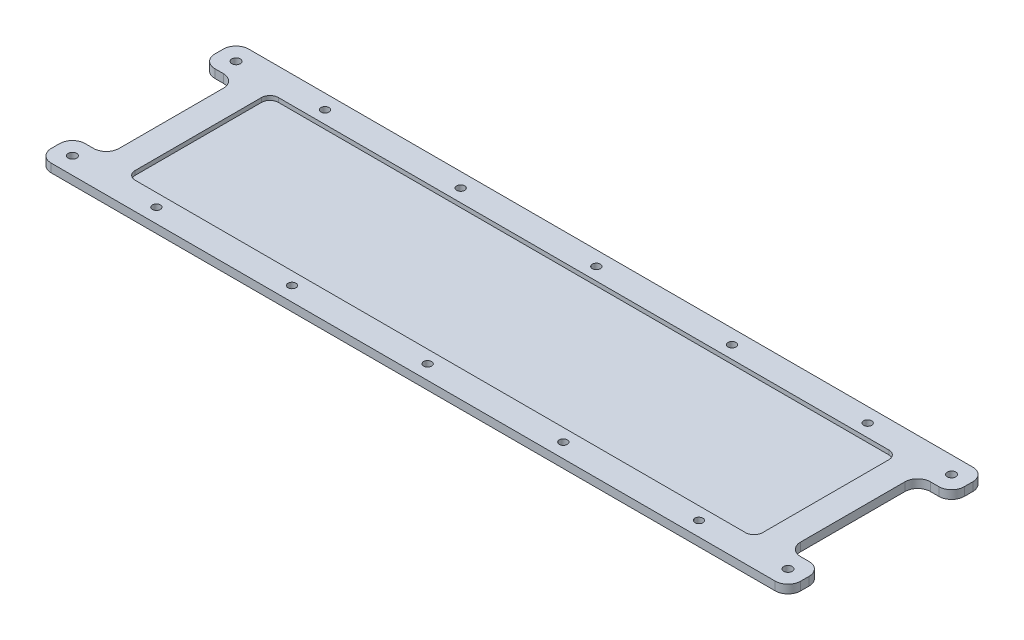
SolidWorks part; units mm, degrees
ref_plane "Front Plane" through (0, 0, 0) normal (0, 0, 1) x (1, 0, 0)
ref_plane "Top Plane" through (0, 0, 0) normal (0, 1, 0) x (1, 0, 0)
ref_plane "Right Plane" through (0, 0, 0) normal (1, 0, 0) x (0, 0, -1)
sketch "Sketch1" plane through (0, 0, 0) normal (0, 1, 0) x (1, 0, 0)
  line L0 (3.81, 3.81) -> (3.81, 70.1599) construction
  line L1 (0, 0) -> (255.27, 0)
  line L2 (0, 0) -> (0, 73.9699)
  line L3 (0, 73.9699) -> (255.27, 73.9699)
  line L4 (255.27, 0) -> (255.27, 73.9699)
  line L5 (6.985, 66.9849) -> (195.485, 66.9849) construction
  line L6 (6.985, 66.9849) -> (6.985, 6.985) construction
  line L7 (6.985, 6.985) -> (195.485, 6.985) construction
  line L8 (195.485, 66.9849) -> (195.485, 6.985) construction
  line L9 (3.81, 70.1599) -> (251.46, 70.1599) construction
  line L10 (251.46, 3.81) -> (251.46, 70.1599) construction
  line L11 (3.81, 3.81) -> (251.46, 3.81) construction
  line L12 (565.2908, 402.2635) -> (1930.6241, 402.2635) construction
  line L28 (127.635, 73.9699) -> (127.635, 0) construction
  line L29 (127.635, 70.1599) -> (127.635, 66.9849) construction
  line L30 (0, 36.9849) -> (255.27, 36.9849) construction
  circle A0 centre (178.435, 68.5724) radius 1.5
  circle A1 centre (178.435, 5.3975) radius 1.5
  circle A2 centre (229.235, 68.5724) radius 1.5
  circle A3 centre (229.235, 5.3975) radius 1.5
  circle A4 centre (214.6468, 59.9999) radius 3.81 construction
  circle A15 centre (127.635, 68.5724) radius 1.5
  circle A20 centre (127.635, 5.3975) radius 1.5
  circle A21 centre (26.035, 5.3975) radius 1.5
  circle A22 centre (76.835, 5.3975) radius 1.5
  circle A23 centre (26.035, 68.5724) radius 1.5
  circle A24 centre (76.835, 68.5724) radius 1.5
  point P48 (127.635, 68.5724)
  dimension "D6" = 3.175
  dimension "D11" = 7.62
  dimension "D13" = 188.5
  dimension "D15" = 3
  dimension "D1" = 59.9999
  dimension "D2" = 3.175
  dimension "D3" = 3.175
  dimension "D4" = 3.81
  dimension "D5" = 3.81
  dimension "D7" = 3.81
  dimension "D8" = 3.81
  dimension "D9" = 19.1618
  dimension "D10" = 10.16
  dimension "D12" = 73.9699
  dimension "D14" = 55.975
  dimension "D16" = 3
  dimension "D17" = 50.8
extrude "Boss-Extrude1" add sketch "Sketch1" along normal blind 1.5875 and the other way blind 1.5875 contours L4 | L2 | L1 L4 L3 L2 A23 A22 A21 A3 A2 A0 A1 A15 A20 A24 region at (127.635, 0, -36.9849)
extrude "Boss-Extrude2" add sketch "Sketch1<4>" along normal blind 1.5875 and the other way blind 1.5875 contours L1 L4 L3 L2
sketch "Sketch1<4>" plane through (0, 0, 0) normal (0, 1, 0) x (1, 0, 0) same geometry as "Sketch1"
sketch "Sketch2" plane through (0, 1.5875, 0) normal (0, 1, 0) x (1, 0, 0)
  line L0 (6.985, 66.9849) -> (195.485, 66.9849) construction
  line L1 (13.335, 63.8099) -> (241.935, 63.8099)
  line L2 (10.16, 60.6349) -> (10.16, 13.335)
  line L3 (13.335, 10.16) -> (241.935, 10.16)
  line L4 (245.11, 60.6349) -> (245.11, 13.335)
  line L5 (6.985, 6.985) -> (195.485, 6.985) construction
  line L6 (6.985, 66.9849) -> (6.985, 6.985) construction
  line L7 (251.46, 3.81) -> (251.46, 70.1599) construction
  line L8 (0, 73.9699) -> (255.27, 73.9699) construction
  arc A0 (241.935, 63.8099) -> (245.11, 60.6349) centre (241.935, 60.6349) cw
  arc A1 (245.11, 13.335) -> (241.935, 10.16) centre (241.935, 13.335) cw
  arc A2 (13.335, 10.16) -> (10.16, 13.335) centre (13.335, 13.335) cw
  arc A3 (13.335, 63.8099) -> (10.16, 60.6349) centre (13.335, 60.6349) ccw
  dimension "D6" = 3.175
  dimension "D1" = 3.175
  dimension "D2" = 3.175
  dimension "D3" = 3.175
  dimension "D4" = 6.35
  dimension "D5" = 10.16
extrude "Cut-Extrude1" cut sketch "Sketch2" against normal blind 1.5875
extrude "Cut-Extrude2" cut sketch "Sketch1<6>" against normal blind 3.175 and the other way blind 3.175 contours A2 | A3 | A1 | A0 | A15 | A24 | A22 | A20 | A21 | A23
sketch "Sketch1<6>" plane through (0, 0, 0) normal (0, 1, 0) x (1, 0, 0) same geometry as "Sketch1"
sketch "Sketch3" plane through (0, -1.5875, 0) normal (0, -1, 0) x (1, 0, 0)
  line L0 (127.635, -36.9849) -> (127.635, 0) construction
  line L5 (0, 0) -> (0, -73.9699) construction
  line L6 (0, -17.4625) -> (0, 0)
  line L8 (0, 0) -> (-7.9375, 0)
  line L9 (0, -36.9849) -> (255.27, -36.9849) construction
  line L10 (255.27, 0) -> (255.27, -73.9699) construction
  line L11 (0, 0) -> (255.27, 0) construction
  line L12 (-12.7, -4.7625) -> (-12.7, -7.9375)
  line L13 (-7.9375, -12.7) -> (-4.7625, -12.7)
  line L14 (-12.7, -6.35) -> (0, -6.35) construction
  line L15 (-12.7, -67.6199) -> (0, -67.6199) construction
  line L16 (-7.9375, -61.2699) -> (-4.7625, -61.2699)
  line L17 (-12.7, -69.2074) -> (-12.7, -66.0324)
  line L18 (0, -73.9699) -> (-7.9375, -73.9699)
  line L19 (0, -56.5074) -> (0, -73.9699)
  line L20 (267.97, -67.6199) -> (255.27, -67.6199) construction
  line L21 (267.97, -6.35) -> (255.27, -6.35) construction
  line L22 (255.27, -56.5074) -> (255.27, -73.9699)
  line L23 (255.27, -73.9699) -> (263.2075, -73.9699)
  line L24 (267.97, -69.2074) -> (267.97, -66.0324)
  line L25 (263.2075, -61.2699) -> (260.0325, -61.2699)
  line L26 (263.2075, -12.7) -> (260.0325, -12.7)
  line L27 (267.97, -4.7625) -> (267.97, -7.9375)
  line L28 (255.27, 0) -> (263.2075, 0)
  line L29 (255.27, -17.4625) -> (255.27, 0)
  arc A4 (0, -17.4625) -> (-4.7625, -12.7) centre (-4.7625, -17.4625) ccw
  arc A5 (-7.9375, 0) -> (-12.7, -4.7625) centre (-7.9375, -4.7625) ccw
  arc A6 (-12.7, -7.9375) -> (-7.9375, -12.7) centre (-7.9375, -7.9375) ccw
  circle A7 centre (-6.35, -6.35) radius 1.5875
  circle A8 centre (-6.35, -67.6199) radius 1.5875
  arc A9 (-12.7, -66.0324) -> (-7.9375, -61.2699) centre (-7.9375, -66.0324) cw
  arc A10 (-7.9375, -73.9699) -> (-12.7, -69.2074) centre (-7.9375, -69.2074) cw
  arc A11 (0, -56.5074) -> (-4.7625, -61.2699) centre (-4.7625, -56.5074) cw
  arc A12 (255.27, -56.5074) -> (260.0325, -61.2699) centre (260.0325, -56.5074) ccw
  arc A13 (263.2075, -73.9699) -> (267.97, -69.2074) centre (263.2075, -69.2074) ccw
  arc A14 (267.97, -66.0324) -> (263.2075, -61.2699) centre (263.2075, -66.0324) ccw
  circle A15 centre (261.62, -67.6199) radius 1.5875
  circle A16 centre (261.62, -6.35) radius 1.5875
  arc A17 (267.97, -7.9375) -> (263.2075, -12.7) centre (263.2075, -7.9375) cw
  arc A18 (263.2075, 0) -> (267.97, -4.7625) centre (263.2075, -4.7625) cw
  arc A19 (255.27, -17.4625) -> (260.0325, -12.7) centre (260.0325, -17.4625) cw
  point P67 (0, 0)
  dimension "D3" = 12.7
  dimension "D5" = 3.175
  dimension "D1" = 4.7625
  dimension "D2" = 4.7625
  dimension "D4" = 12.7
extrude "Boss-Extrude3" add sketch "Sketch3" against normal blind 3.175 contours A4 A11 L16 A9 L17 A10 L18 A8 | L12 A6 L13 A4 L8 A5 A7 | L9 A19 L26 A17 L27 A18 L28 A16 | L24 A14 L25 A12 L9 L23 A13 A15 region at (-1.2422, -1.5875, -13.9422) region at (-6.35, -1.5875, -61.4858) region at (256.5122, -1.5875, -60.0277) region at (261.62, -1.5875, -12.4841)
